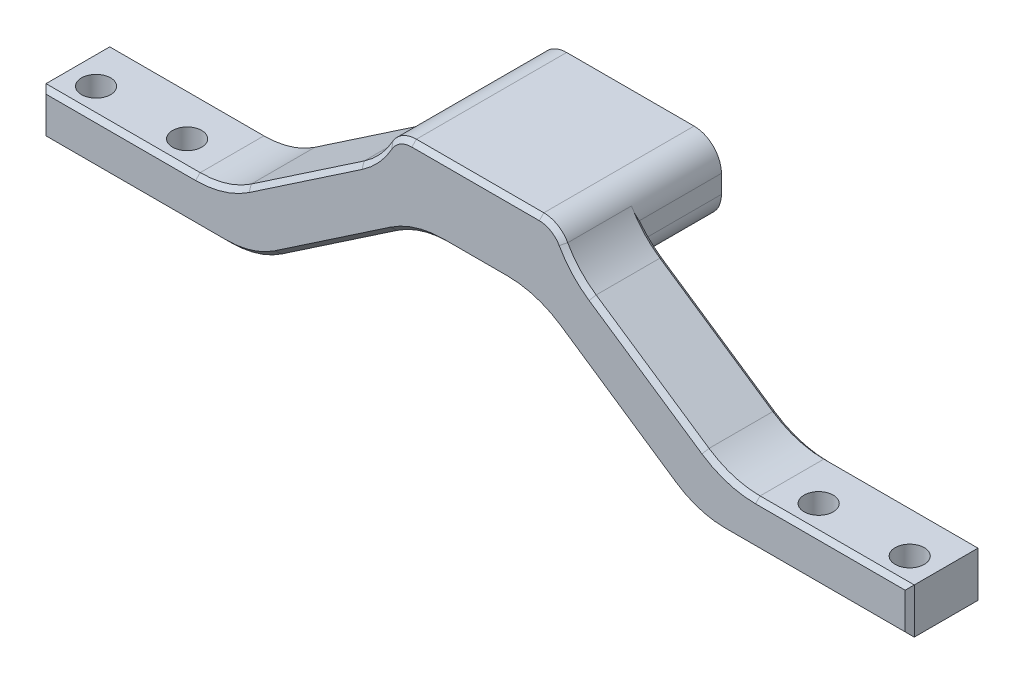
SolidWorks part; units mm, degrees
material "5052-H38"
ref_plane "Front" through (0, 0, 0) normal (0, 0, 1) x (1, 0, 0)
ref_plane "Top" through (0, 0, 0) normal (0, 1, 0) x (1, 0, 0)
ref_plane "Right" through (0, 0, 0) normal (1, 0, 0) x (0, 0, -1)
sketch "ｽｹｯﾁ2" plane through (0, 0, 0) normal (0, 0, 1) x (1, 0, 0)
  line L4 (87.5, 41.7504) -> (73.5, 41.7504)
  line L5 (70.5, 38.7504) -> (70.5, 36.7504)
  line L6 (73.5, 33.7504) -> (87.5, 33.7504)
  line L7 (90.5, 36.7504) -> (90.5, 38.7504)
  line L8 (87.5, 41.7504) -> (73.5, 41.7504)
  line L9 (70.5, 38.7504) -> (70.5, 36.7504)
  line L10 (73.5, 33.7504) -> (87.5, 33.7504)
  line L11 (90.5, 36.7504) -> (90.5, 38.7504)
  arc A4 (90.5, 38.7504) -> (87.5, 41.7504) centre (87.5, 38.7504) ccw
  arc A5 (73.5, 41.7504) -> (70.5, 38.7504) centre (73.5, 38.7504) ccw
  arc A6 (70.5, 36.7504) -> (73.5, 33.7504) centre (73.5, 36.7504) ccw
  arc A7 (87.5, 33.7504) -> (90.5, 36.7504) centre (87.5, 36.7504) ccw
  arc A8 (90.5, 38.7504) -> (87.5, 41.7504) centre (87.5, 38.7504) ccw
  arc A9 (73.5, 41.7504) -> (70.5, 38.7504) centre (73.5, 38.7504) ccw
  arc A10 (70.5, 36.7504) -> (73.5, 33.7504) centre (73.5, 36.7504) ccw
  arc A11 (87.5, 33.7504) -> (90.5, 36.7504) centre (87.5, 36.7504) ccw
  dimension "D1" = 0
extrude "ﾎﾞｽ - 押し出し1" add sketch "ｽｹｯﾁ2" along normal blind 17
sketch "ｽｹｯﾁ5" plane through (0, 0, 17) normal (0, 0, 1) x (1, 0, 0)
  line L0 (74.5, 37.7504) -> (54.5, 24.2096) construction
  line L1 (56.1819, 21.7254) -> (76.1819, 35.2662)
  line L2 (56.1819, 21.7254) -> (52.8181, 26.6938) construction
  line L3 (76.1819, 35.2662) -> (72.8181, 40.2346)
  line L4 (52.8181, 26.6938) -> (72.8181, 40.2346)
  line L5 (56.1819, 21.7254) -> (72.8181, 40.2346) construction
  line L6 (76.1819, 35.2662) -> (52.8181, 26.6938) construction
  line L7 (80.5, 41.7504) -> (80.5, 33.7004) construction
  line L8 (87.5, 41.7504) -> (73.5, 41.7504) construction
  line L9 (84.8181, 35.2662) -> (108.1819, 26.6938) construction
  line L10 (104.8181, 21.7254) -> (88.1819, 40.2346) construction
  line L11 (86.5, 37.7504) -> (106.5, 24.2096) construction
  line L12 (108.1819, 26.6938) -> (88.1819, 40.2346)
  line L13 (84.8181, 35.2662) -> (88.1819, 40.2346)
  line L14 (104.8181, 21.7254) -> (108.1819, 26.6938) construction
  line L15 (104.8181, 21.7254) -> (84.8181, 35.2662)
  line L16 (35.2152, 21.7254) -> (119.9925, 21.7254) construction
  line L17 (52.8181, 26.6938) -> (32.8181, 26.6938)
  line L18 (32.8181, 26.6938) -> (32.8181, 21.7254)
  line L19 (32.8181, 21.7254) -> (56.1819, 21.7254)
  line L20 (128.1819, 21.7254) -> (104.8181, 21.7254)
  line L21 (128.1819, 26.6938) -> (128.1819, 21.7254)
  line L22 (108.1819, 26.6938) -> (128.1819, 26.6938)
  arc A0 (105.9294, 18.5905) -> (55.0706, 18.5905) centre (80.5, 0.0004) ccw construction
  arc A1 (105.9294, 18.5905) -> (55.0706, 18.5905) centre (80.5, 0.0004) ccw construction
  point P4 (64.5, 30.98)
  point P22 (96.5, 30.98)
  point P25 (80.5, 37.7254)
  dimension "D1" = 20
  dimension "D2" = 20
  dimension "D3" = 6
  dimension "D4" = 16
extrude "ﾎﾞｽ - 押し出し3" add sketch "ｽｹｯﾁ5" against normal blind 8
sketch "ｽｹｯﾁ7" plane through (0, 0, 17) normal (0, 0, 1) x (1, 0, 0)
  circle A0 centre (74.5, 37.7504) radius 1.6 construction
  circle A1 centre (86.5, 37.7504) radius 1.6 construction
  circle A2 centre (74.5, 37.7504) radius 1.6
  circle A3 centre (86.5, 37.7504) radius 1.6
hole_wizard "M3x0.5 ねじ穴2" positions "ｽｹｯﾁ10" profile "ｽｹｯﾁ12" tap size "M3x0.5" standard "JIS"
sketch "ｽｹｯﾁ10" plane through (0, 0, 0) normal (0, 0, -1) x (-1, 0, 0)
  point P0 (-86.5, 37.7504)
  point P3 (-74.5, 37.7504)
sketch "ｽｹｯﾁ12" plane through (86.5, 37.7504, 0) normal (1, 0, 0) x (0, 1, 0)
  line L0 (0, 0) -> (0, 9.2511)
  line L1 (0, 9.2511) -> (1.25, 8.5)
  line L2 (1.25, 8.5) -> (1.25, 0)
  line L5 (1.25, 0) -> (0, 0)
  line L10 (0, 9.2511) -> (-1.25, 8.5) construction
  line L11 (0, -6.35) -> (0, 107.95) construction
  dimension "ねじ下穴ﾄﾞﾘﾙ直径" = 2.5
  dimension "ねじ下穴ﾄﾞﾘﾙの深さ" = 8.5
  dimension "ﾄﾞﾘﾙ角度" = 118
cosmetic thread "穴のねじ山2" parameters "D1"=6, "D2"=3
cosmetic thread "穴のねじ山3" parameters "D1"=6, "D2"=3
fillet "ﾌｨﾚｯﾄ3" radius 10 6 edges at (73.943, 33.7504, 13) (87.057, 33.7504, 13) (52.8181, 26.6938, 13) (56.1819, 21.7254, 13) (108.1819, 26.6938, 13) (104.8181, 21.7254, 13)
fillet "ﾌｨﾚｯﾄ4" radius 10 2 edges at (70.5, 38.6651, 13) (90.5, 38.6651, 13)
chamfer "面取り2" distance 0.5 angle 45 18 edges at (119.7153, 26.6938, 9) (108.3167, 27.1332, 9) (91.4824, 38.3269, 9) (99.4434, 32.6101, 9) (118.0334, 21.7254, 9) (86.9222, 33.3109, 9) (104.9529, 22.1649, 9) (95.9375, 27.7379, 9) (42.9666, 21.7254, 9) (56.0471, 22.1649, 9) (74.0778, 33.3109, 9) (65.0625, 27.7379, 9) (69.5176, 38.3269, 9) (61.5566, 32.6101, 9) (52.6833, 27.1332, 9) (41.2847, 26.6938, 9) (32.8181, 24.2096, 9) (128.1819, 24.2096, 9)
chamfer "面取り3" distance 0.5 angle 45 22 edges at (32.8181, 24.2096, 17) (41.2847, 26.6938, 17) (52.6833, 27.1332, 17) (61.5566, 32.6101, 17) (69.5176, 38.3269, 17) (71.9813, 41.3376, 17) (80.5, 41.7504, 17) (89.0187, 41.3376, 17) (91.4824, 38.3269, 17) (99.4434, 32.6101, 17) (108.3167, 27.1332, 17) (119.7153, 26.6938, 17) (128.1819, 24.2096, 17) (118.0334, 21.7254, 17) (104.9529, 22.1649, 17) (95.9375, 27.7379, 17) (86.9222, 33.3109, 17) (80.5, 33.7504, 17) (74.0778, 33.3109, 17) (65.0625, 27.7379, 17) (56.0471, 22.1649, 17) (42.9666, 21.7254, 17)
sketch "ｽｹｯﾁ13" plane through (0, 41.7504, 0) normal (0, 1, 0) x (1, 0, 0)
  line L0 (32.8181, -14) -> (128.1819, -14) construction
  line L1 (32.8181, -9.5) -> (32.8181, -16.5) construction
  line L3 (80.5, 0) -> (80.5, -17) construction
  line L4 (87.5, 0) -> (73.5, 0) construction
  line L5 (87.5, -17) -> (73.5, -17) construction
  line L7 (49.7513, -17) -> (33.3181, -17) construction
  circle A0 centre (35.8181, -14) radius 1.5
  circle A1 centre (125.1819, -14) radius 1.5
  circle A2 centre (45.8181, -14) radius 1.5
  circle A3 centre (115.1819, -14) radius 1.5
  point P4 (32.8181, -13)
  point P21 (0, 0)
  point P22 (35.8181, -14)
  dimension "D1" = 3
  dimension "D2" = 3
  dimension "D3" = 10
  dimension "D4" = 3
hole_wizard "M3 すきま穴1" positions "ｽｹｯﾁ14" profile "ｽｹｯﾁ15" hole size "M3" standard "JIS"
sketch "ｽｹｯﾁ14" plane through (0, 26.6938, 0) normal (0, 1, 0) x (1, 0, 0)
  point P0 (35.8181, -14)
  point P3 (125.1819, -14)
  point P7 (45.8181, -14)
  point P10 (115.1819, -14)
sketch "ｽｹｯﾁ15" plane through (35.8181, 26.6938, 14) normal (1, 0, 0) x (0, 0, 1)
  line L0 (0, 0) -> (0, 9.4614)
  line L1 (0, 9.4614) -> (1.6, 8.5)
  line L2 (1.6, 8.5) -> (1.6, 0)
  line L5 (1.6, 0) -> (0, 0)
  line L10 (0, 9.4614) -> (-1.6, 8.5) construction
  line L11 (0, -6.35) -> (0, 107.95) construction
  dimension "穴の直径" = 3.2
  dimension "穴の深さ" = 8.5
  dimension "ﾄﾞﾘﾙ角度" = 118
